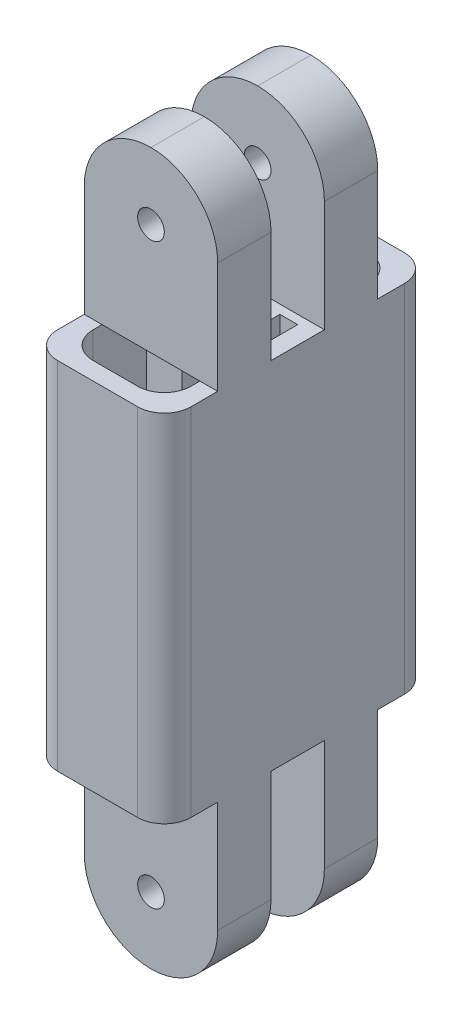
SolidWorks part; units mm, degrees
ref_plane "Front Plane" through (0, 0, 0) normal (0, 0, 1) x (1, 0, 0)
ref_plane "Top Plane" through (0, 0, 0) normal (0, 1, 0) x (1, 0, 0)
ref_plane "Right Plane" through (0, 0, 0) normal (1, 0, 0) x (0, 0, -1)
sketch "Sketch1" plane through (0, 0, 0) normal (0, 1, 0) x (1, 0, 0)
  line L0 (0, 0) -> (-10.7454, 0) construction
  line L1 (-7.5, -15) -> (7.5, -15)
  line L2 (-7.5, -15) -> (-7.5, 15)
  line L3 (-7.5, 15) -> (7.5, 15)
  line L4 (7.5, -15) -> (7.5, 15)
  line L5 (-7.5, -15) -> (7.5, 15) construction
  line L6 (-7.5, 15) -> (7.5, -15) construction
  line L7 (-5.5, -13) -> (5.5, -13)
  line L8 (-5.5, -13) -> (-5.5, -4)
  line L9 (-5.5, 13) -> (5.5, 13)
  line L10 (5.5, -13) -> (5.5, -4)
  line L11 (-5.5, -13) -> (5.5, 13) construction
  line L12 (-5.5, 13) -> (5.5, -13) construction
  line L13 (-10.7454, 0) -> (11.7241, 0) construction
  line L14 (-5.5, 4) -> (-1.5, 4)
  line L15 (-1.5, 4) -> (-1.5, -4)
  line L16 (-1.5, -4) -> (-5.5, -4)
  line L17 (-5.5, 2) -> (-3.5, 2)
  line L18 (-3.5, 2) -> (-3.5, -2)
  line L19 (-3.5, -2) -> (-5.5, -2)
  line L20 (5.5, 4) -> (1.5, 4)
  line L21 (1.5, 4) -> (1.5, -4)
  line L22 (1.5, -4) -> (5.5, -4)
  line L23 (5.5, 2) -> (3.5, 2)
  line L24 (3.5, 2) -> (3.5, -2)
  line L25 (3.5, -2) -> (5.5, -2)
  line L26 (-5.5, 4) -> (-5.5, 13)
  line L27 (5.5, 4) -> (5.5, 13)
  line L28 (-5.5, 2) -> (-5.5, -2)
  line L29 (5.5, 2) -> (5.5, -2)
  point P0 (0, 0)
  point P6 (0, 0)
  dimension "D1" = 2
  dimension "D2" = 2
  dimension "D3" = 2
  dimension "D4" = 2
  dimension "D5" = 2
  dimension "D6" = 2
  dimension "D7" = 2
  dimension "D8" = 2
  dimension "D9" = 2
  dimension "D10" = 2
  dimension "D11" = 15
  dimension "D12" = 30
  dimension "D13" = 8
  dimension "D14" = 8
  dimension "D15" = 2
extrude "Boss-Extrude1" add sketch "Sketch1" along normal blind 40 from offset 20 offset against normal yes
sketch "Sketch2" plane through (0, -20, 0) normal (0, -1, 0) x (1, 0, 0)
  line L0 (-7.5, -15) -> (-7.5, 15) construction
  line L3 (7.5, 9) -> (-7.5, 9)
  line L8 (7.5, -9) -> (-7.5, -9)
  line L11 (-7.5, -9) -> (-7.5, -3)
  line L12 (-7.5, -3) -> (7.5, -3)
  line L13 (7.5, 15) -> (7.5, -15) construction
  line L14 (7.5, -3) -> (7.5, -9)
  line L15 (-7.5, 9) -> (-7.5, 3)
  line L16 (-7.5, 3) -> (7.5, 3)
  line L17 (7.5, 3) -> (7.5, 9)
  line L18 (-7.5, 15) -> (7.5, 15) construction
  line L19 (7.5, -15) -> (-7.5, -15) construction
  dimension "D1" = 6
  dimension "D2" = 6
  dimension "D3" = 6
  dimension "D4" = 6
extrude "Boss-Extrude2" add sketch "Sketch2" along normal blind 20
fillet "Fillet1" radius 7.5 4 edges at (7.5, -40, 6) (7.5, -40, -6) (-7.5, -40, 6) (-7.5, -40, -6)
sketch "Sketch3" plane through (0, 0, 9) normal (0, 0, 1) x (1, 0, 0)
  circle A1 centre (0, -32.5) radius 1.5
  dimension "D1" = 3
extrude "Cut-Extrude1" cut sketch "Sketch3" against normal through all
mirror "Mirror1" about plane through (0, 0, 0) normal (0, 1, 0) of "Boss-Extrude2", "Cut-Extrude1", "Fillet1"
fillet "Fillet2" radius 3 8 edges at (-5.5, 0, 13) (5.5, 0, 13) (5.5, 0, -13) (-5.5, 0, -13) (-7.5, 0, -15) (-7.5, 0, 15) (7.5, 0, 15) (7.5, 0, -15)
